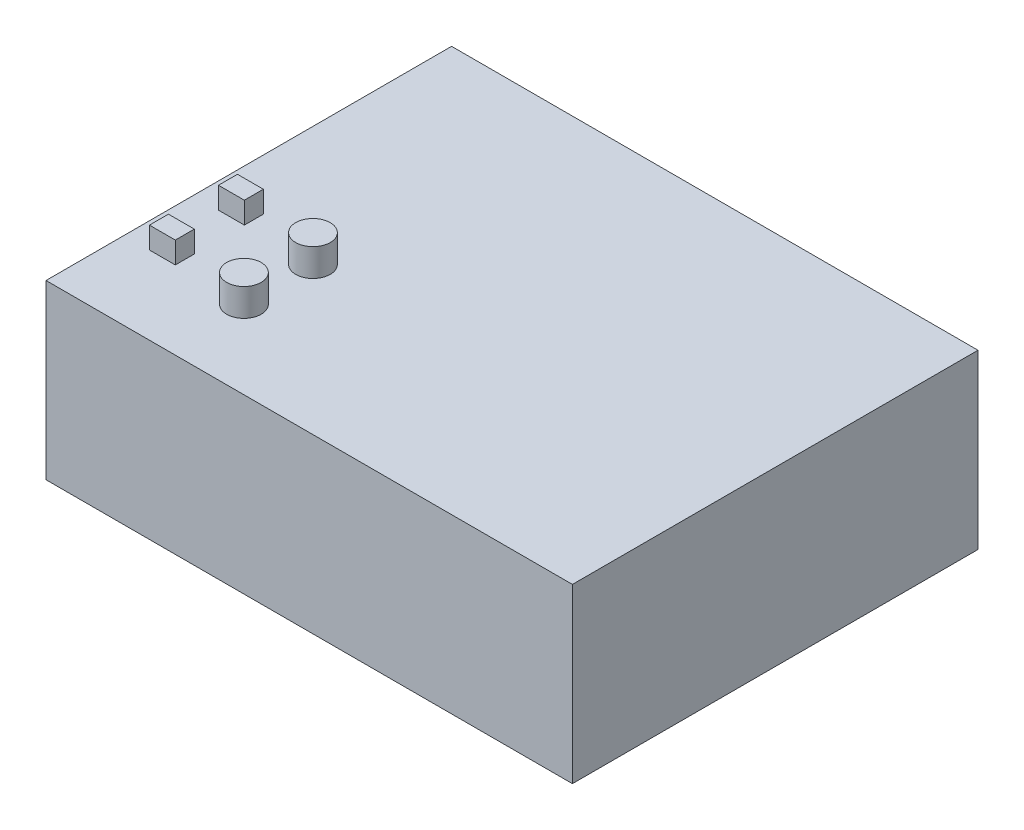
SolidWorks part; units mm, degrees
ref_plane "Front Plane" through (0, 0, 0) normal (0, 0, 1) x (1, 0, 0)
ref_plane "Top Plane" through (0, 0, 0) normal (0, 1, 0) x (1, 0, 0)
ref_plane "Right Plane" through (0, 0, 0) normal (1, 0, 0) x (0, 0, -1)
sketch "Sketch1" plane through (0, 0, 0) normal (0, 1, 0) x (1, 0, 0)
  line L1 (-30.5, -23.5) -> (30.5, -23.5)
  line L2 (-30.5, -23.5) -> (-30.5, 23.5)
  line L3 (-30.5, 23.5) -> (30.5, 23.5)
  line L4 (30.5, -23.5) -> (30.5, 23.5)
  line L5 (-30.5, -23.5) -> (30.5, 23.5) construction
  line L6 (-30.5, 23.5) -> (30.5, -23.5) construction
  point P0 (0, 0)
  dimension "D1" = 61
  dimension "D2" = 47
extrude "Boss-Extrude1" add sketch "Sketch1" along normal blind 20
sketch "Sketch2" plane through (0, 0, 0) normal (0, 1, 0) x (1, 0, 0)
  line L0 (-30.5, 23.5) -> (-30.5, -23.5) construction
  line L1 (-30.5, -23.5) -> (30.5, -23.5) construction
  circle A0 centre (-16.64, -14.425) radius 2
  circle A1 centre (-16.64, -6.425) radius 2
  dimension "D1" = 4
  dimension "D2" = 4
  dimension "D3" = 8
  dimension "D4" = 13.86
  dimension "D5" = 9.075
extrude "Boss-Extrude2" add sketch "Sketch2" along normal blind 23.2
sketch "Sketch3" plane through (0, 20, 0) normal (0, 1, 0) x (1, 0, 0)
  line L1 (-27.565, -4.25) -> (-24.565, -4.25)
  line L2 (-27.565, -4.25) -> (-27.565, -6.45)
  line L3 (-27.565, -6.45) -> (-24.565, -6.45)
  line L4 (-24.565, -4.25) -> (-24.565, -6.45)
  line L5 (-27.565, -4.25) -> (-24.565, -6.45) construction
  line L6 (-27.565, -6.45) -> (-24.565, -4.25) construction
  line L7 (-27.565, -12.25) -> (-24.565, -12.25)
  line L8 (-27.565, -12.25) -> (-27.565, -14.45)
  line L9 (-27.565, -14.45) -> (-24.565, -14.45)
  line L10 (-24.565, -12.25) -> (-24.565, -14.45)
  line L11 (-27.565, -12.25) -> (-24.565, -14.45) construction
  line L12 (-27.565, -14.45) -> (-24.565, -12.25) construction
  circle A1 centre (-16.64, -14.425) radius 2 construction
  circle A2 centre (-16.64, -14.425) radius 2 construction
  point P0 (-26.065, -5.35)
  point P5 (-26.065, -13.35)
  dimension "D5" = 9.425
  dimension "D1" = 3
  dimension "D2" = 3
  dimension "D3" = 2.2
  dimension "D4" = 2.2
  dimension "D6" = 1.075
  dimension "D7" = 8
  dimension "D8" = 0
extrude "Boss-Extrude3" add sketch "Sketch3" along normal blind 2.5
